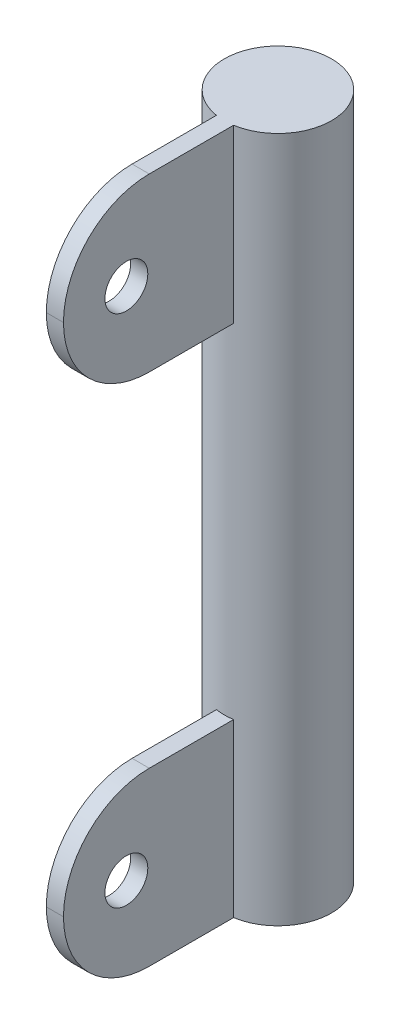
SolidWorks part; units mm, degrees
ref_plane "Front Plane" through (0, 0, 0) normal (0, 0, 1) x (1, 0, 0)
ref_plane "Top Plane" through (0, 0, 0) normal (0, 1, 0) x (1, 0, 0)
ref_plane "Right Plane" through (0, 0, 0) normal (1, 0, 0) x (0, 0, -1)
sketch "Sketch1" plane through (0, 0, 0) normal (0, 1, 0) x (1, 0, 0)
  circle A0 centre (0, 0) radius 12.5
  dimension "D1" = 25
extrude "Boss-Extrude1" add sketch "Sketch1" along normal blind 160
ref_plane "Plane1" through (0, 0, 12) normal (0, 0, 1) x (1, 0, 0)
sketch "Sketch2" plane through (0, 0, 12) normal (0, 0, 1) x (1, 0, 0)
  line L0 (12.5, 160) -> (-12.5, 160) construction
  line L1 (12.5, 160) -> (-12.5, 160)
  line L2 (0, 160) -> (0, 124.7931) construction
  line L3 (-2, 160) -> (2, 160)
  line L4 (-2, 160) -> (-2, 120)
  line L5 (-2, 120) -> (2, 120)
  line L6 (2, 160) -> (2, 120)
  point P9 (0, 120)
  dimension "D1" = 40
  dimension "D2" = 4
extrude "Boss-Extrude2" add sketch "Sketch2" along normal blind 40 contours L4 L5 L6 L3
fillet "Fillet1" radius 20 2 edges at (0, 120, 52) (0, 160, 52)
sketch "Sketch3" plane through (2, 0, 0) normal (1, 0, 0) x (0, 0, -1)
  line L0 (-12.339, 160) -> (-12.339, 120) construction
  line L1 (-52, 140) -> (-21.6124, 140) construction
  circle A0 centre (-37.339, 140) radius 5
  point P4 (0, 0)
  dimension "D1" = 10
  dimension "D2" = 25
extrude "Cut-Extrude1" cut sketch "Sketch3" against normal through all
ref_plane "Plane2" through (0, 80, 0) normal (0, 1, 0) x (1, 0, 0)
mirror "Mirror2" about plane through (0, 80, 0) normal (0, 1, 0) of "Cut-Extrude1", "Fillet1", "Boss-Extrude2"
